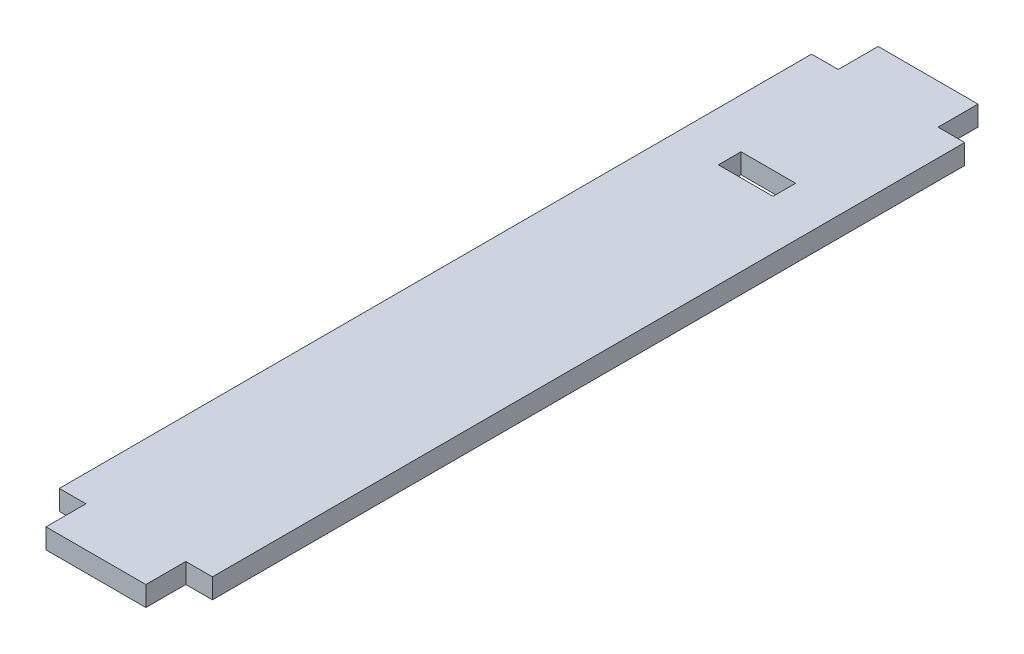
SolidWorks part; units mm, degrees
material "AISI 304"
ref_plane "Front Plane" through (0, 0, 0) normal (0, 0, 1) x (1, 0, 0)
ref_plane "Top Plane" through (0, 0, 0) normal (0, 1, 0) x (1, 0, 0)
ref_plane "Right Plane" through (0, 0, 0) normal (1, 0, 0) x (0, 0, -1)
sketch "Sketch1" plane through (0, 0, 0) normal (0, 1, 0) x (1, 0, 0)
  line L0 (3.75, 28.25) -> (5.75, 28.25)
  line L1 (-5.75, -28.25) -> (-3.75, -28.25)
  line L2 (-5.75, -28.25) -> (-5.75, -16.6)
  line L3 (-5.75, 28.25) -> (-3.75, 28.25)
  line L4 (5.75, -28.25) -> (5.75, -14.1)
  line L5 (-5.75, -28.25) -> (5.75, 28.25) construction
  line L6 (-5.75, 28.25) -> (5.75, -28.25) construction
  line L8 (3.75, 28.25) -> (3.75, 31.25)
  line L9 (3.75, 31.25) -> (-3.75, 31.25)
  line L10 (-3.75, 28.25) -> (-3.75, 31.25)
  line L12 (-3.75, -28.25) -> (-3.75, -31.25)
  line L13 (-3.75, -31.25) -> (3.75, -31.25)
  line L14 (3.75, -28.25) -> (3.75, -31.25)
  line L15 (3.75, -28.25) -> (5.75, -28.25)
  line L16 (-5.75, -14.9) -> (-5.75, 28.25)
  line L21 (5.75, -12.4) -> (5.75, 28.25)
  line L26 (0, 0) -> (0, 53.4412) construction
  line L31 (-5.75, -16.6) -> (-5.75, -14.9)
  line L32 (-2.05, 17.55) -> (2.05, 17.55)
  line L33 (-2.05, 17.55) -> (-2.05, 19.25)
  line L34 (-2.05, 19.25) -> (2.05, 19.25)
  line L35 (2.05, 17.55) -> (2.05, 19.25)
  line L36 (-2.05, 17.55) -> (2.05, 19.25) construction
  line L37 (-2.05, 19.25) -> (2.05, 17.55) construction
  line L38 (5.75, -12.4) -> (5.75, -14.1)
  point P0 (0, 0)
  point P23 (0, 18.4)
  dimension "D1" = 7.5
  dimension "D2" = 2
  dimension "D3" = 2
  dimension "D4" = 3
  dimension "D5" = 2
  dimension "D6" = 2
  dimension "D7" = 3
  dimension "D8" = 56.5
  dimension "D11" = 1.7
  dimension "D12" = 3.7
  dimension "D13" = 12
extrude "Boss-Extrude1" add sketch "Sketch1" along normal blind 1.5
